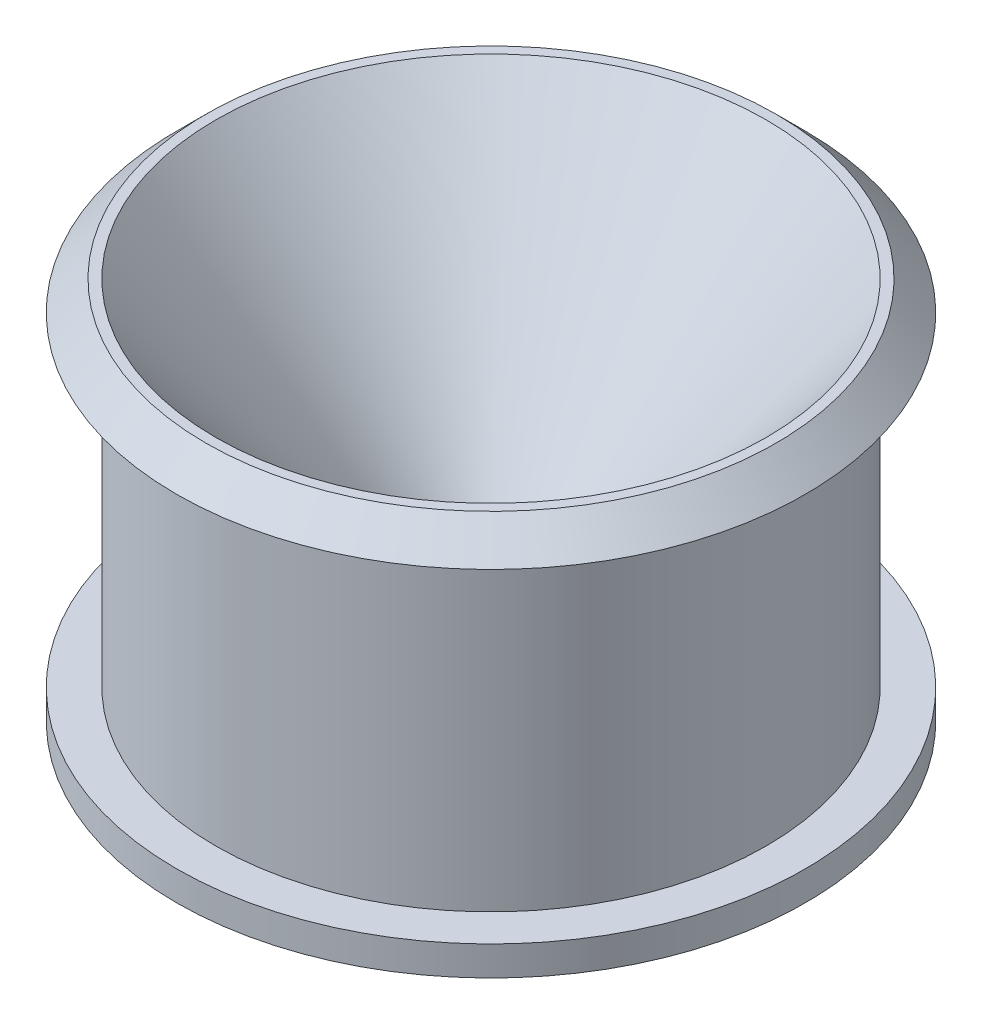
SolidWorks part; units mm, degrees
ref_plane "Front Plane" through (0, 0, 0) normal (0, 0, 1) x (1, 0, 0)
ref_plane "Top Plane" through (0, 0, 0) normal (0, 1, 0) x (1, 0, 0)
ref_plane "Right Plane" through (0, 0, 0) normal (1, 0, 0) x (0, 0, -1)
sketch "Sketch2" plane through (0, 0, 0) normal (0, 0, 1) x (1, 0, 0)
  line L0 (-3, 0) -> (-3, 8)
  line L1 (-3, 8) -> (-28, 39)
  line L2 (-28, 39) -> (-28, 0)
  line L3 (-28, 0) -> (-3, 0)
  line L4 (-7, 12.96) -> (-7, 8)
  line L5 (-7, 8) -> (-3, 8)
  line L6 (0, 0) -> (0, 6.3637)
  line L8 (-28, 0) -> (-32, 0)
  line L9 (-28, 0) -> (-28, 3)
  line L10 (-28, 3) -> (-32, 3)
  line L11 (-32, 0) -> (-32, 3)
  line L12 (-28, 39) -> (-32, 39)
  line L13 (-28, 39) -> (-28, 36)
  line L14 (-28, 36) -> (-32, 36)
  line L15 (-32, 39) -> (-32, 36)
  point P0 (0, 0)
  dimension "D1" = 8
  dimension "D2" = 3
  dimension "D3" = 25
  dimension "D4" = 39
  dimension "D5" = 7
  dimension "D6" = 4
  dimension "D7" = 4
  dimension "D8" = 3
  dimension "D9" = 3
revolve "Revolve1" add sketch "Sketch2" angle 360 about L6 region at (-18.4643, 13.5192, 0) region at (-30, 1.5, 0) region at (-30, 37.5, 0)
chamfer "Chamfer1" distance 3 angle 45 1 edges at (0, 39, -32)
